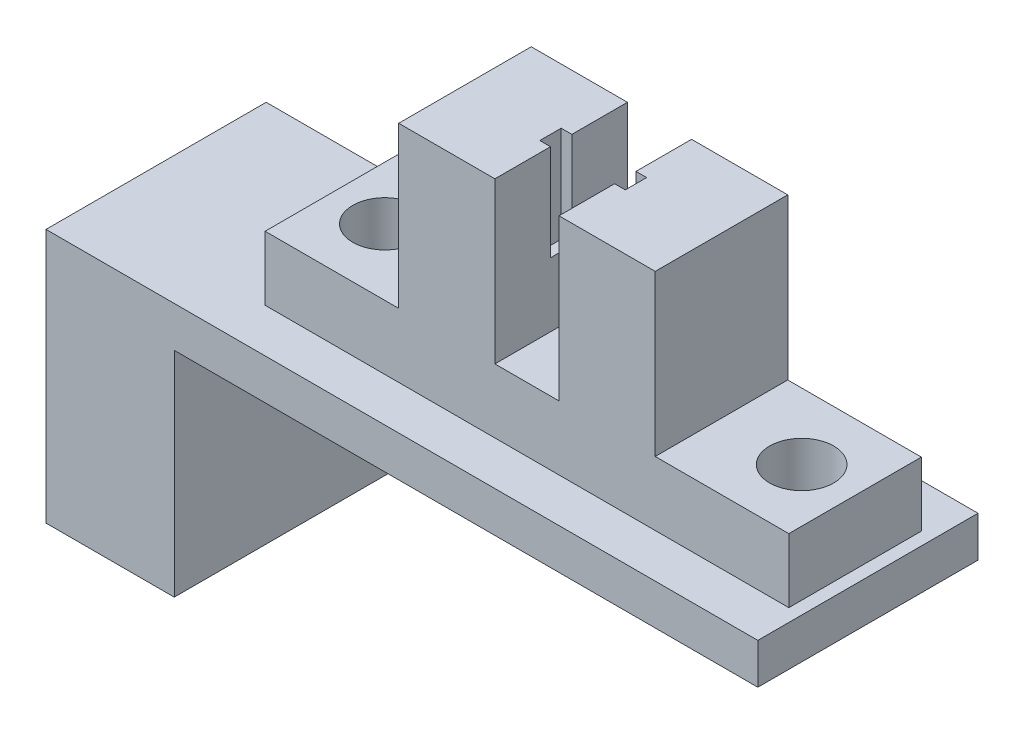
SolidWorks part; units mm, degrees
ref_plane "Front Plane" through (0, 0, 0) normal (0, 0, 1) x (1, 0, 0)
ref_plane "Top Plane" through (0, 0, 0) normal (0, 1, 0) x (1, 0, 0)
ref_plane "Right Plane" through (0, 0, 0) normal (1, 0, 0) x (0, 0, -1)
sketch "Sketch1" plane through (0, 0, 0) normal (0, 1, 0) x (1, 0, 0)
  line L1 (-16.65, -5.15) -> (16.65, -5.15)
  line L2 (-16.65, -5.15) -> (-16.65, 5.15)
  line L3 (-16.65, 5.15) -> (16.65, 5.15)
  line L4 (16.65, -5.15) -> (16.65, 5.15)
  line L5 (-16.65, -5.15) -> (16.65, 5.15) construction
  line L6 (-16.65, 5.15) -> (16.65, -5.15) construction
  point P0 (0, 0)
  dimension "D1" = 33.3
  dimension "D2" = 10.3
extrude "Boss-Extrude1" add sketch "Sketch1" along normal blind 1.9
sketch "Sketch2" plane through (0, 1.9, 0) normal (0, 1, 0) x (1, 0, 0)
  line L0 (16.65, -5.15) -> (16.65, 5.15) construction
  line L1 (-8.45, 3.1) -> (16.05, 3.1)
  line L2 (-8.45, 3.1) -> (-8.45, -3.1)
  line L3 (-8.45, -3.1) -> (16.05, -3.1)
  line L4 (16.05, 3.1) -> (16.05, -3.1)
  circle A0 centre (-5.95, 0) radius 1.5
  circle A1 centre (13.55, 0) radius 1.5
  point P6 (-8.45, 0)
  dimension "D4" = 3
  dimension "D1" = 0.6
  dimension "D2" = 6.2
  dimension "D3" = 24.5
  dimension "D5" = 2.5
  dimension "D6" = 2.5
extrude "Boss-Extrude2" add sketch "Sketch2" along normal blind 3
sketch "Sketch3" plane through (0, 4.9, 0) normal (0, 1, 0) x (1, 0, 0)
  line L0 (16.05, 3.1) -> (-8.45, 3.1) construction
  line L1 (-2.2, 3.1) -> (2.3, 3.1)
  line L2 (-2.2, 3.1) -> (-2.2, -3.1)
  line L3 (-2.2, -3.1) -> (2.3, -3.1)
  line L4 (9.8, 3.1) -> (9.8, -3.1)
  line L5 (-8.45, -3.1) -> (16.05, -3.1) construction
  line L6 (16.05, 3.1) -> (-8.45, 3.1) construction
  line L7 (5.3, 3.1) -> (5.3, -3.1)
  line L8 (2.3, 3.1) -> (2.3, -3.1)
  line L9 (5.3, 3.1) -> (9.8, 3.1)
  line L10 (5.3, -3.1) -> (9.8, -3.1)
  dimension "D1" = 12
  dimension "D2" = 4.5
  dimension "D3" = 4.5
extrude "Boss-Extrude3" add sketch "Sketch3" along normal blind 7.5
sketch "Sketch4" plane through (0, 0, 0) normal (0, -1, 0) x (1, 0, 0)
  line L0 (16.65, -5.15) -> (-16.65, -5.15) construction
  line L1 (-16.65, 5.15) -> (-10.65, 5.15)
  line L2 (-16.65, 5.15) -> (-16.65, -5.15)
  line L3 (-16.65, -5.15) -> (-10.65, -5.15)
  line L4 (-10.65, 5.15) -> (-10.65, -5.15)
  dimension "D1" = 6
extrude "Boss-Extrude4" add sketch "Sketch4" along normal blind 10
sketch "Sketch5" plane through (0, 0, 0) normal (0, -1, 0) x (1, 0, 0)
  line L0 (3.8, 8.9004) -> (3.8, -10.316) construction
  line L1 (2.3, 3.1) -> (5.3, 3.1) construction
  circle A0 centre (-0.925, 1.7268) radius 1
  circle A1 centre (-0.925, -0.9732) radius 1
  circle A2 centre (8.525, -0.9732) radius 1
  circle A3 centre (8.525, 1.7268) radius 1
  point P4 (3.8, 3.1)
  dimension "D1" = 2
  dimension "D2" = 2.7
  dimension "D3" = 4.725
extrude "Boss-Extrude5" add sketch "Sketch5" along normal blind 2 draft 22
sketch "Sketch6" plane through (0, 12.4, 0) normal (0, 1, 0) x (1, 0, 0)
  line L0 (2.3, -3.1) -> (2.3, 3.1) construction
  line L1 (1.8, 0.5) -> (5.8, 0.5)
  line L2 (1.8, 0.5) -> (1.8, -0.5)
  line L3 (1.8, -0.5) -> (5.8, -0.5)
  line L4 (5.8, 0.5) -> (5.8, -0.5)
  line L5 (16.05, 3.1) -> (-8.45, 3.1) construction
  point P6 (2.3, 0)
  point P7 (1.8, 0)
  point P8 (3.8, 0.5)
  point P11 (3.8, 3.1)
  dimension "D1" = 4
  dimension "D2" = 1
extrude "Cut-Extrude1" cut sketch "Sketch6" against normal blind 4.5
extrude "Cut-Extrude2" cut sketch "Sketch2<2>" against normal up to next contours A1 | A0 region at (-5.95, 1.9, 0) region at (13.55, 1.9, 0)
sketch "Sketch2<2>" plane through (0, 1.9, 0) normal (0, 1, 0) x (1, 0, 0) same geometry as "Sketch2"
